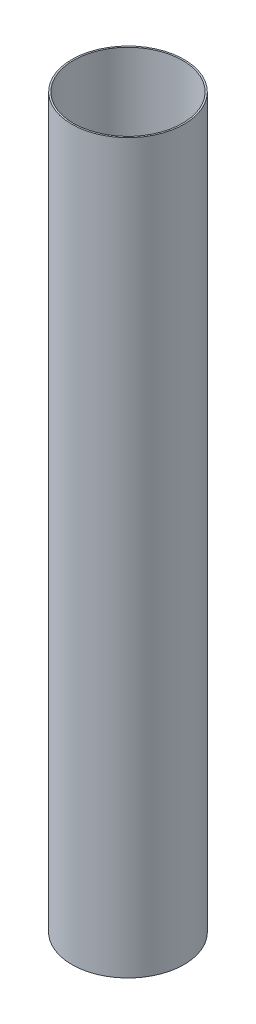
SolidWorks part; units mm, degrees
material "E-Glass Fiber"
ref_plane "Front Plane" through (0, 0, 0) normal (0, 0, 1) x (1, 0, 0)
ref_plane "Top Plane" through (0, 0, 0) normal (0, 1, 0) x (1, 0, 0)
ref_plane "Right Plane" through (0, 0, 0) normal (1, 0, 0) x (0, 0, -1)
sketch "Body Tube Profile" plane through (0, 0, 0) normal (0, 1, 0) x (1, 0, 0)
  circle A0 centre (0, 0) radius 76.2
  circle A1 centre (0, 0) radius 78.359
  dimension "D1" = 152.4
  dimension "D2" = 156.718
extrude "Body Tube Extrustion" [suppressed] add sketch "Body Tube Profile" along normal blind 914.4
extrude "Boss-Extrude1" add sketch "Body Tube Profile<2>" along normal blind 1016
sketch "Body Tube Profile<2>" plane through (0, 0, 0) normal (0, 1, 0) x (1, 0, 0) same geometry as "Body Tube Profile"
equation "\"Length\"= 36"
equation "\"Outer Diameter\"= 6.17"
equation "\"Inner Diameter\"= 6"
equation "\"Wall Thickness\"= 0.085"
equation "\"D1@Body Tube Profile\" = \"Inner Diameter\""
equation "\"D2@Body Tube Profile\" = \"Outer Diameter\""
equation "\"D1@Body Tube Extrustion\" = \"Length\""
